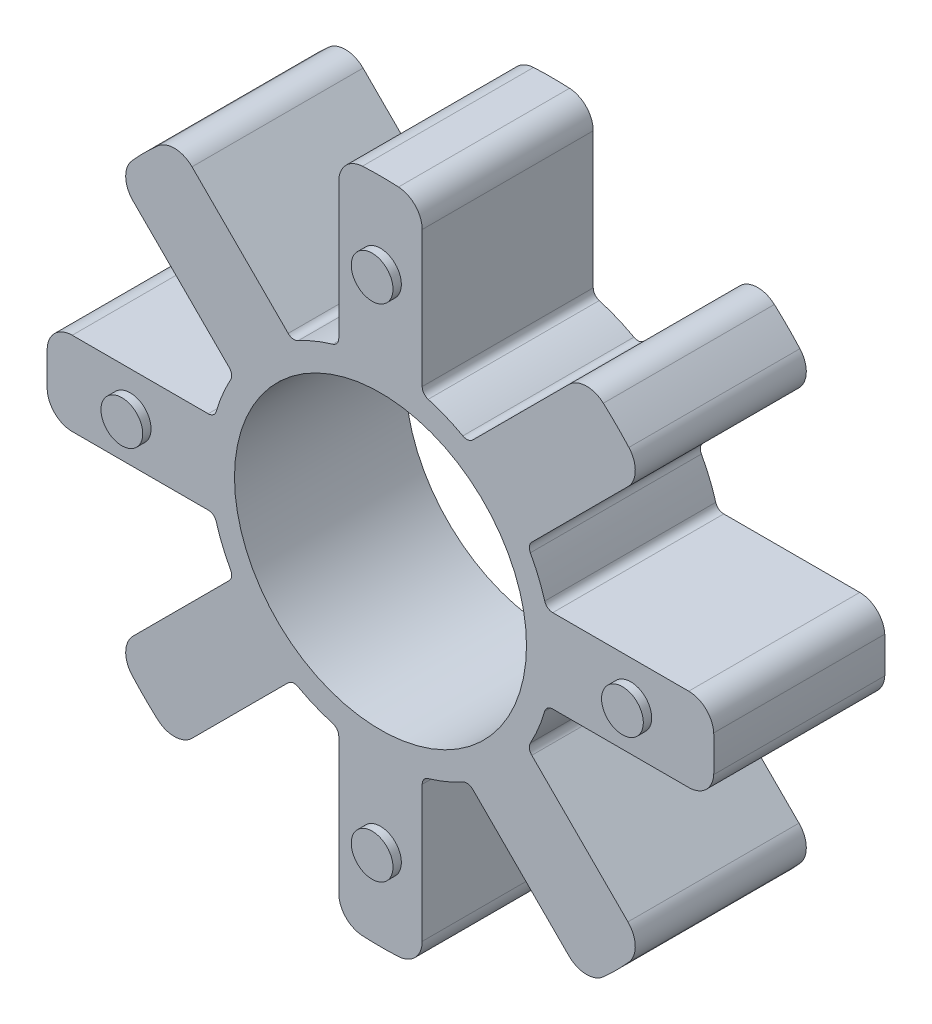
SolidWorks part; units mm, degrees
ref_plane "Front Plane" through (0, 0, 0) normal (0, 0, 1) x (1, 0, 0)
ref_plane "Top Plane" through (0, 0, 0) normal (0, 1, 0) x (1, 0, 0)
ref_plane "Right Plane" through (0, 0, 0) normal (1, 0, 0) x (0, 0, -1)
sketch "Sketch1" plane through (0, 0, 0) normal (0, 0, 1) x (1, 0, 0)
  line L0 (-5, 39.6863) -> (-5, 19.8809)
  line L1 (5, 39.6863) -> (5, 19.8809)
  line L2 (0, 47.6697) -> (0, -47.6697) construction
  line L3 (24.5269, 31.598) -> (10.5224, 17.5934)
  line L4 (31.598, 24.5269) -> (17.5934, 10.5224)
  line L5 (39.6863, 5) -> (19.8809, 5)
  line L6 (39.6863, -5) -> (19.8809, -5)
  line L7 (31.598, -24.5269) -> (17.5934, -10.5224)
  line L8 (24.5269, -31.598) -> (10.5224, -17.5934)
  line L9 (5, -39.6863) -> (5, -19.8809)
  line L10 (-5, -39.6863) -> (-5, -19.8809)
  line L11 (-24.5269, -31.598) -> (-10.5224, -17.5934)
  line L12 (-31.598, -24.5269) -> (-17.5934, -10.5224)
  line L13 (-39.6863, -5) -> (-19.8809, -5)
  line L14 (-39.6863, 5) -> (-19.8809, 5)
  line L15 (-31.598, 24.5269) -> (-17.5934, 10.5224)
  line L16 (-24.5269, 31.598) -> (-10.5224, 17.5934)
  arc A0 (-24.5269, 31.598) -> (-31.598, 24.5269) centre (0, 0) ccw
  circle A1 centre (0, 0) radius 17.5
  circle A2 centre (0, 0) radius 20.5
  arc A3 (5, 39.6863) -> (-5, 39.6863) centre (0, 0) ccw
  arc A4 (31.598, 24.5269) -> (24.5269, 31.598) centre (0, 0) ccw
  arc A5 (39.6863, -5) -> (39.6863, 5) centre (0, 0) ccw
  arc A6 (24.5269, -31.598) -> (31.598, -24.5269) centre (0, 0) ccw
  arc A7 (-5, -39.6863) -> (5, -39.6863) centre (0, 0) ccw
  arc A8 (-39.6863, 5) -> (-39.6863, -5) centre (0, 0) ccw
  arc A9 (-31.598, -24.5269) -> (-24.5269, -31.598) centre (0, 0) ccw
  point P12 (0, 0)
  point P43 (0, 0)
  dimension "D1" = 80
  dimension "D2" = 35
  dimension "D3" = 41
  dimension "D4" = 10
  dimension "D5" = 8
extrude "Boss-Extrude1" add sketch "Sketch1" along normal mid plane 20.5 contours A2 L16 A0 L15 | L2 A3 L0 A2 | A3 L2 A2 L1 | L4 A4 L3 A2 | L6 A5 L5 A2 | L8 A6 L7 A2 | A2 L2 A7 L9 | L2 A2 L10 A7 | L12 A9 L11 A2 | L14 A8 L13 A2 | L2 A2 A1 | A2 L2 A1 region at (-2.5065, 30.0946, 0) region at (-2.4628, 19.8897, 0) region at (2.5065, 30.0946, 0) region at (-21.2801, 21.2801, 0) region at (2.4628, 19.8897, 0) region at (-30.0946, 0, 0) region at (21.2801, 21.2801, 0) region at (2.5065, -30.0946, 0) region at (-2.5065, -30.0946, 0) region at (-21.2801, -21.2801, 0) region at (30.0946, 0, 0) region at (21.2801, -21.2801, 0)
fillet "Fillet1" radius 1 16 edges at (-10.5224, 17.5934, 0) (-5, 19.8809, 0) (-17.5934, 10.5224, 0) (-19.8809, 5, 0) (-19.8809, -5, 0) (-17.5934, -10.5224, 0) (-5, -19.8809, 0) (-10.5224, -17.5934, 0) (5, -19.8809, 0) (10.5224, -17.5934, 0) (17.5934, -10.5224, 0) (19.8809, -5, 0) (19.8809, 5, 0) (17.5934, 10.5224, 0) (10.5224, 17.5934, 0) (5, 19.8809, 0)
fillet "Fillet2" radius 3 16 edges at (31.598, -24.5269, 0) (24.5269, -31.598, 0) (5, -39.6863, 0) (-5, -39.6863, 0) (-24.5269, -31.598, 0) (-31.598, -24.5269, 0) (-39.6863, -5, 0) (-39.6863, 5, 0) (-31.598, 24.5269, 0) (-24.5269, 31.598, 0) (-5, 39.6863, 0) (5, 39.6863, 0) (24.5269, 31.598, 0) (31.598, 24.5269, 0) (39.6863, -5, 0) (39.6863, 5, 0)
sketch "Sketch2" plane through (0, 0, 0) normal (0, 0, 1) x (1, 0, 0)
  circle A0 centre (0, 0) radius 30 construction
  circle A1 centre (-30, 0) radius 2.5
  circle A2 centre (0, 30) radius 2.5
  circle A3 centre (30, 0) radius 2.5
  circle A4 centre (0, -30) radius 2.5
  point P14 (0, 0)
  dimension "D1" = 60
  dimension "D2" = 5
  dimension "D3" = 4
extrude "Boss-Extrude2" add sketch "Sketch2" along normal mid plane 22.5
